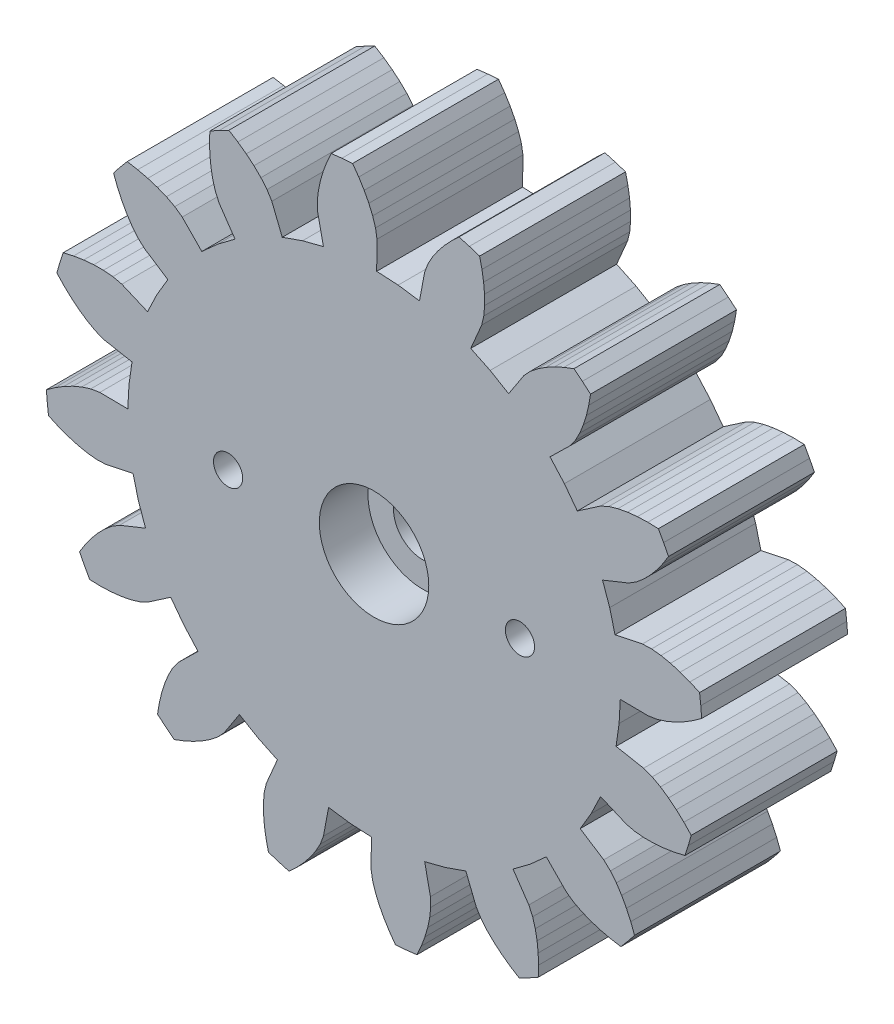
SolidWorks part; units mm, degrees
ref_plane "Front Plane" through (0, 0, 0) normal (0, 0, 1) x (1, 0, 0)
ref_plane "Top Plane" through (0, 0, 0) normal (0, 1, 0) x (1, 0, 0)
ref_plane "Right Plane" through (0, 0, 0) normal (1, 0, 0) x (0, 0, -1)
sketch "Sketch1" plane through (0, 0, 0) normal (0, 0, 1) x (1, 0, 0)
  line L0 (0.1087, 10.1244) -> (0.1211, 11.2757)
  line L1 (0.1211, 11.2757) -> (0.0606, 11.6468)
  line L2 (0.0606, 11.6468) -> (-0.0565, 12.0174)
  line L3 (-0.0565, 12.0174) -> (-0.2135, 12.3863)
  line L4 (-0.2135, 12.3863) -> (-0.4052, 12.7523)
  line L5 (-0.4052, 12.7523) -> (-0.6285, 13.1143)
  line L6 (-0.6285, 13.1143) -> (-0.8817, 13.4712)
  line L7 (-0.8817, 13.4712) -> (-1.3232, 13.435)
  line L8 (-1.3232, 13.435) -> (-1.7633, 13.3843)
  line L9 (-1.7633, 13.3843) -> (-1.942, 12.985)
  line L10 (-1.942, 12.985) -> (-2.0905, 12.5863)
  line L11 (-2.0905, 12.5863) -> (-2.207, 12.19)
  line L12 (-2.207, 12.19) -> (-2.2891, 11.7975)
  line L13 (-2.2891, 11.7975) -> (-2.3316, 11.4112)
  line L14 (-2.3316, 11.4112) -> (-2.3185, 11.0354)
  line L15 (-2.3185, 11.0354) -> (-2.0818, 9.9087)
  line L16 (-2.0818, 9.9087) -> (-2.9391, 9.689)
  line L17 (-2.9391, 9.689) -> (-3.774, 9.3953)
  line L18 (-3.774, 9.3953) -> (-4.2031, 10.4637)
  line L19 (-4.2031, 10.4637) -> (-4.4011, 10.7834)
  line L20 (-4.4011, 10.7834) -> (-4.6511, 11.081)
  line L21 (-4.6511, 11.081) -> (-4.9373, 11.3617)
  line L22 (-4.9373, 11.3617) -> (-5.2544, 11.6266)
  line L23 (-5.2544, 11.6266) -> (-5.5993, 11.8755)
  line L24 (-5.5993, 11.8755) -> (-5.9698, 12.1083)
  line L25 (-5.9698, 12.1083) -> (-6.3639, 11.9059)
  line L26 (-6.3639, 11.9059) -> (-6.7511, 11.6907)
  line L27 (-6.7511, 11.6907) -> (-6.7633, 11.2534)
  line L28 (-6.7633, 11.2534) -> (-6.7479, 10.8283)
  line L29 (-6.7479, 10.8283) -> (-6.7039, 10.4175)
  line L30 (-6.7039, 10.4175) -> (-6.6295, 10.0235)
  line L31 (-6.6295, 10.0235) -> (-6.521, 9.6503)
  line L32 (-6.521, 9.6503) -> (-6.3651, 9.3081)
  line L33 (-6.3651, 9.3081) -> (-5.7152, 8.3577)
  line L34 (-5.7152, 8.3577) -> (-6.4232, 7.8267)
  line L35 (-6.4232, 7.8267) -> (-7.0822, 7.2359)
  line L36 (-7.0822, 7.2359) -> (-7.8875, 8.0587)
  line L37 (-7.8875, 8.0587) -> (-8.1927, 8.2783)
  line L38 (-8.1927, 8.2783) -> (-8.5375, 8.4576)
  line L39 (-8.5375, 8.4576) -> (-8.9094, 8.6074)
  line L40 (-8.9094, 8.6074) -> (-9.3038, 8.7308)
  line L41 (-9.3038, 8.7308) -> (-9.7177, 8.8288)
  line L42 (-9.7177, 8.8288) -> (-10.149, 8.9021)
  line L43 (-10.149, 8.9021) -> (-10.4356, 8.5643)
  line L44 (-10.4356, 8.5643) -> (-10.711, 8.2173)
  line L45 (-10.711, 8.2173) -> (-10.555, 7.8085)
  line L46 (-10.555, 7.8085) -> (-10.3781, 7.4217)
  line L47 (-10.3781, 7.4217) -> (-10.1802, 7.059)
  line L48 (-10.1802, 7.059) -> (-9.9607, 6.7235)
  line L49 (-9.9607, 6.7235) -> (-9.7176, 6.4202)
  line L50 (-9.7176, 6.4202) -> (-9.4426, 6.1637)
  line L51 (-9.4426, 6.1637) -> (-8.4785, 5.5344)
  line L52 (-8.4785, 5.5344) -> (-8.9295, 4.7729)
  line L53 (-8.9295, 4.7729) -> (-9.3121, 3.9749)
  line L54 (-9.3121, 3.9749) -> (-10.371, 4.4269)
  line L55 (-10.371, 4.4269) -> (-10.737, 4.513)
  line L56 (-10.737, 4.513) -> (-11.1243, 4.5467)
  line L57 (-11.1243, 4.5467) -> (-11.5252, 4.5427)
  line L58 (-11.5252, 4.5427) -> (-11.9367, 4.5058)
  line L59 (-11.9367, 4.5058) -> (-12.3566, 4.438)
  line L60 (-12.3566, 4.438) -> (-12.7832, 4.3406)
  line L61 (-12.7832, 4.3406) -> (-12.9187, 3.9188)
  line L62 (-12.9187, 3.9188) -> (-13.0403, 3.4929)
  line L63 (-13.0403, 3.4929) -> (-12.7397, 3.1749)
  line L64 (-12.7397, 3.1749) -> (-12.4283, 2.8853)
  line L65 (-12.4283, 2.8853) -> (-12.1067, 2.6259)
  line L66 (-12.1067, 2.6259) -> (-11.7755, 2.3999)
  line L67 (-11.7755, 2.3999) -> (-11.4348, 2.2128)
  line L68 (-11.4348, 2.2128) -> (-11.0826, 2.081)
  line L69 (-11.0826, 2.081) -> (-9.9511, 1.8685)
  line L70 (-9.9511, 1.8685) -> (-10.0762, 0.9924)
  line L71 (-10.0762, 0.9924) -> (-10.1244, 0.1087)
  line L72 (-10.1244, 0.1087) -> (-11.2757, 0.1211)
  line L73 (-11.2757, 0.1211) -> (-11.6468, 0.0606)
  line L74 (-11.6468, 0.0606) -> (-12.0174, -0.0565)
  line L75 (-12.0174, -0.0565) -> (-12.3863, -0.2135)
  line L76 (-12.3863, -0.2135) -> (-12.7523, -0.4052)
  line L77 (-12.7523, -0.4052) -> (-13.1143, -0.6285)
  line L78 (-13.1143, -0.6285) -> (-13.4712, -0.8817)
  line L79 (-13.4712, -0.8817) -> (-13.435, -1.3232)
  line L80 (-13.435, -1.3232) -> (-13.3843, -1.7633)
  line L81 (-13.3843, -1.7633) -> (-12.985, -1.942)
  line L82 (-12.985, -1.942) -> (-12.5863, -2.0905)
  line L83 (-12.5863, -2.0905) -> (-12.19, -2.207)
  line L84 (-12.19, -2.207) -> (-11.7975, -2.2891)
  line L85 (-11.7975, -2.2891) -> (-11.4112, -2.3316)
  line L86 (-11.4112, -2.3316) -> (-11.0354, -2.3185)
  line L87 (-11.0354, -2.3185) -> (-9.9087, -2.0818)
  line L88 (-9.9087, -2.0818) -> (-9.689, -2.9391)
  line L89 (-9.689, -2.9391) -> (-9.3953, -3.774)
  line L90 (-9.3953, -3.774) -> (-10.4637, -4.2031)
  line L91 (-10.4637, -4.2031) -> (-10.7834, -4.4011)
  line L92 (-10.7834, -4.4011) -> (-11.081, -4.6511)
  line L93 (-11.081, -4.6511) -> (-11.3617, -4.9373)
  line L94 (-11.3617, -4.9373) -> (-11.6266, -5.2544)
  line L95 (-11.6266, -5.2544) -> (-11.8755, -5.5993)
  line L96 (-11.8755, -5.5993) -> (-12.1083, -5.9698)
  line L97 (-12.1083, -5.9698) -> (-11.9059, -6.3639)
  line L98 (-11.9059, -6.3639) -> (-11.6907, -6.7511)
  line L99 (-11.6907, -6.7511) -> (-11.2534, -6.7633)
  line L100 (-11.2534, -6.7633) -> (-10.8283, -6.7479)
  line L101 (-10.8283, -6.7479) -> (-10.4175, -6.7039)
  line L102 (-10.4175, -6.7039) -> (-10.0235, -6.6295)
  line L103 (-10.0235, -6.6295) -> (-9.6503, -6.521)
  line L104 (-9.6503, -6.521) -> (-9.3081, -6.3651)
  line L105 (-9.3081, -6.3651) -> (-8.3577, -5.7152)
  line L106 (-8.3577, -5.7152) -> (-7.8267, -6.4232)
  line L107 (-7.8267, -6.4232) -> (-7.2359, -7.0822)
  line L108 (-7.2359, -7.0822) -> (-8.0587, -7.8875)
  line L109 (-8.0587, -7.8875) -> (-8.2783, -8.1927)
  line L110 (-8.2783, -8.1927) -> (-8.4576, -8.5375)
  line L111 (-8.4576, -8.5375) -> (-8.6074, -8.9094)
  line L112 (-8.6074, -8.9094) -> (-8.7308, -9.3038)
  line L113 (-8.7308, -9.3038) -> (-8.8288, -9.7177)
  line L114 (-8.8288, -9.7177) -> (-8.9021, -10.149)
  line L115 (-8.9021, -10.149) -> (-8.5643, -10.4356)
  line L116 (-8.5643, -10.4356) -> (-8.2173, -10.711)
  line L117 (-8.2173, -10.711) -> (-7.8085, -10.555)
  line L118 (-7.8085, -10.555) -> (-7.4217, -10.3781)
  line L119 (-7.4217, -10.3781) -> (-7.059, -10.1802)
  line L120 (-7.059, -10.1802) -> (-6.7235, -9.9607)
  line L121 (-6.7235, -9.9607) -> (-6.4202, -9.7176)
  line L122 (-6.4202, -9.7176) -> (-6.1637, -9.4426)
  line L123 (-6.1637, -9.4426) -> (-5.5344, -8.4785)
  line L124 (-5.5344, -8.4785) -> (-4.7729, -8.9295)
  line L125 (-4.7729, -8.9295) -> (-3.9749, -9.3121)
  line L126 (-3.9749, -9.3121) -> (-4.4269, -10.371)
  line L127 (-4.4269, -10.371) -> (-4.513, -10.737)
  line L128 (-4.513, -10.737) -> (-4.5467, -11.1243)
  line L129 (-4.5467, -11.1243) -> (-4.5427, -11.5252)
  line L130 (-4.5427, -11.5252) -> (-4.5058, -11.9367)
  line L131 (-4.5058, -11.9367) -> (-4.438, -12.3566)
  line L132 (-4.438, -12.3566) -> (-4.3406, -12.7832)
  line L133 (-4.3406, -12.7832) -> (-3.9188, -12.9187)
  line L134 (-3.9188, -12.9187) -> (-3.4929, -13.0403)
  line L135 (-3.4929, -13.0403) -> (-3.1749, -12.7397)
  line L136 (-3.1749, -12.7397) -> (-2.8853, -12.4283)
  line L137 (-2.8853, -12.4283) -> (-2.6259, -12.1067)
  line L138 (-2.6259, -12.1067) -> (-2.3999, -11.7755)
  line L139 (-2.3999, -11.7755) -> (-2.2128, -11.4348)
  line L140 (-2.2128, -11.4348) -> (-2.081, -11.0826)
  line L141 (-2.081, -11.0826) -> (-1.8685, -9.9511)
  line L142 (-1.8685, -9.9511) -> (-0.9924, -10.0762)
  line L143 (-0.9924, -10.0762) -> (-0.1087, -10.1244)
  line L144 (-0.1087, -10.1244) -> (-0.1211, -11.2757)
  line L145 (-0.1211, -11.2757) -> (-0.0606, -11.6468)
  line L146 (-0.0606, -11.6468) -> (0.0565, -12.0174)
  line L147 (0.0565, -12.0174) -> (0.2135, -12.3863)
  line L148 (0.2135, -12.3863) -> (0.4052, -12.7523)
  line L149 (0.4052, -12.7523) -> (0.6285, -13.1143)
  line L150 (0.6285, -13.1143) -> (0.8817, -13.4712)
  line L151 (0.8817, -13.4712) -> (1.3232, -13.435)
  line L152 (1.3232, -13.435) -> (1.7633, -13.3843)
  line L153 (1.7633, -13.3843) -> (1.942, -12.985)
  line L154 (1.942, -12.985) -> (2.0905, -12.5863)
  line L155 (2.0905, -12.5863) -> (2.207, -12.19)
  line L156 (2.207, -12.19) -> (2.2891, -11.7975)
  line L157 (2.2891, -11.7975) -> (2.3316, -11.4112)
  line L158 (2.3316, -11.4112) -> (2.3185, -11.0354)
  line L159 (2.3185, -11.0354) -> (2.0818, -9.9087)
  line L160 (2.0818, -9.9087) -> (2.9391, -9.689)
  line L161 (2.9391, -9.689) -> (3.774, -9.3953)
  line L162 (3.774, -9.3953) -> (4.2031, -10.4637)
  line L163 (4.2031, -10.4637) -> (4.4011, -10.7834)
  line L164 (4.4011, -10.7834) -> (4.6511, -11.081)
  line L165 (4.6511, -11.081) -> (4.9373, -11.3617)
  line L166 (4.9373, -11.3617) -> (5.2544, -11.6266)
  line L167 (5.2544, -11.6266) -> (5.5993, -11.8755)
  line L168 (5.5993, -11.8755) -> (5.9698, -12.1083)
  line L169 (5.9698, -12.1083) -> (6.3639, -11.9059)
  line L170 (6.3639, -11.9059) -> (6.7511, -11.6907)
  line L171 (6.7511, -11.6907) -> (6.7633, -11.2534)
  line L172 (6.7633, -11.2534) -> (6.7479, -10.8283)
  line L173 (6.7479, -10.8283) -> (6.7039, -10.4175)
  line L174 (6.7039, -10.4175) -> (6.6295, -10.0235)
  line L175 (6.6295, -10.0235) -> (6.521, -9.6503)
  line L176 (6.521, -9.6503) -> (6.3651, -9.3081)
  line L177 (6.3651, -9.3081) -> (5.7152, -8.3577)
  line L178 (5.7152, -8.3577) -> (6.4232, -7.8267)
  line L179 (6.4232, -7.8267) -> (7.0822, -7.2359)
  line L180 (7.0822, -7.2359) -> (7.8875, -8.0587)
  line L181 (7.8875, -8.0587) -> (8.1927, -8.2783)
  line L182 (8.1927, -8.2783) -> (8.5375, -8.4576)
  line L183 (8.5375, -8.4576) -> (8.9094, -8.6074)
  line L184 (8.9094, -8.6074) -> (9.3038, -8.7308)
  line L185 (9.3038, -8.7308) -> (9.7177, -8.8288)
  line L186 (9.7177, -8.8288) -> (10.149, -8.9021)
  line L187 (10.149, -8.9021) -> (10.4356, -8.5643)
  line L188 (10.4356, -8.5643) -> (10.711, -8.2173)
  line L189 (10.711, -8.2173) -> (10.555, -7.8085)
  line L190 (10.555, -7.8085) -> (10.3781, -7.4217)
  line L191 (10.3781, -7.4217) -> (10.1802, -7.059)
  line L192 (10.1802, -7.059) -> (9.9607, -6.7235)
  line L193 (9.9607, -6.7235) -> (9.7176, -6.4202)
  line L194 (9.7176, -6.4202) -> (9.4426, -6.1637)
  line L195 (9.4426, -6.1637) -> (8.4785, -5.5344)
  line L196 (8.4785, -5.5344) -> (8.9295, -4.7729)
  line L197 (8.9295, -4.7729) -> (9.3121, -3.9749)
  line L198 (9.3121, -3.9749) -> (10.371, -4.4269)
  line L199 (10.371, -4.4269) -> (10.737, -4.513)
  line L200 (10.737, -4.513) -> (11.1243, -4.5467)
  line L201 (11.1243, -4.5467) -> (11.5252, -4.5427)
  line L202 (11.5252, -4.5427) -> (11.9367, -4.5058)
  line L203 (11.9367, -4.5058) -> (12.3566, -4.438)
  line L204 (12.3566, -4.438) -> (12.7832, -4.3406)
  line L205 (12.7832, -4.3406) -> (12.9187, -3.9188)
  line L206 (12.9187, -3.9188) -> (13.0403, -3.4929)
  line L207 (13.0403, -3.4929) -> (12.7397, -3.1749)
  line L208 (12.7397, -3.1749) -> (12.4283, -2.8853)
  line L209 (12.4283, -2.8853) -> (12.1067, -2.6259)
  line L210 (12.1067, -2.6259) -> (11.7755, -2.3999)
  line L211 (11.7755, -2.3999) -> (11.4348, -2.2128)
  line L212 (11.4348, -2.2128) -> (11.0826, -2.081)
  line L213 (11.0826, -2.081) -> (9.9511, -1.8685)
  line L214 (9.9511, -1.8685) -> (10.0762, -0.9924)
  line L215 (10.0762, -0.9924) -> (10.1244, -0.1087)
  line L216 (10.1244, -0.1087) -> (11.2757, -0.1211)
  line L217 (11.2757, -0.1211) -> (11.6468, -0.0606)
  line L218 (11.6468, -0.0606) -> (12.0174, 0.0565)
  line L219 (12.0174, 0.0565) -> (12.3863, 0.2135)
  line L220 (12.3863, 0.2135) -> (12.7523, 0.4052)
  line L221 (12.7523, 0.4052) -> (13.1143, 0.6285)
  line L222 (13.1143, 0.6285) -> (13.4712, 0.8817)
  line L223 (13.4712, 0.8817) -> (13.435, 1.3232)
  line L224 (13.435, 1.3232) -> (13.3843, 1.7633)
  line L225 (13.3843, 1.7633) -> (12.985, 1.942)
  line L226 (12.985, 1.942) -> (12.5863, 2.0905)
  line L227 (12.5863, 2.0905) -> (12.19, 2.207)
  line L228 (12.19, 2.207) -> (11.7975, 2.2891)
  line L229 (11.7975, 2.2891) -> (11.4112, 2.3316)
  line L230 (11.4112, 2.3316) -> (11.0354, 2.3185)
  line L231 (11.0354, 2.3185) -> (9.9087, 2.0818)
  line L232 (9.9087, 2.0818) -> (9.689, 2.9391)
  line L233 (9.689, 2.9391) -> (9.3953, 3.774)
  line L234 (9.3953, 3.774) -> (10.4637, 4.2031)
  line L235 (10.4637, 4.2031) -> (10.7834, 4.4011)
  line L236 (10.7834, 4.4011) -> (11.081, 4.6511)
  line L237 (11.081, 4.6511) -> (11.3617, 4.9373)
  line L238 (11.3617, 4.9373) -> (11.6266, 5.2544)
  line L239 (11.6266, 5.2544) -> (11.8755, 5.5993)
  line L240 (11.8755, 5.5993) -> (12.1083, 5.9698)
  line L241 (12.1083, 5.9698) -> (11.9059, 6.3639)
  line L242 (11.9059, 6.3639) -> (11.6907, 6.7511)
  line L243 (11.6907, 6.7511) -> (11.2534, 6.7633)
  line L244 (11.2534, 6.7633) -> (10.8283, 6.7479)
  line L245 (10.8283, 6.7479) -> (10.4175, 6.7039)
  line L246 (10.4175, 6.7039) -> (10.0235, 6.6295)
  line L247 (10.0235, 6.6295) -> (9.6503, 6.521)
  line L248 (9.6503, 6.521) -> (9.3081, 6.3651)
  line L249 (9.3081, 6.3651) -> (8.3577, 5.7152)
  line L250 (8.3577, 5.7152) -> (7.8267, 6.4232)
  line L251 (7.8267, 6.4232) -> (7.2359, 7.0822)
  line L252 (7.2359, 7.0822) -> (8.0587, 7.8875)
  line L253 (8.0587, 7.8875) -> (8.2783, 8.1927)
  line L254 (8.2783, 8.1927) -> (8.4576, 8.5375)
  line L255 (8.4576, 8.5375) -> (8.6074, 8.9094)
  line L256 (8.6074, 8.9094) -> (8.7308, 9.3038)
  line L257 (8.7308, 9.3038) -> (8.8288, 9.7177)
  line L258 (8.8288, 9.7177) -> (8.9021, 10.149)
  line L259 (8.9021, 10.149) -> (8.5643, 10.4356)
  line L260 (8.5643, 10.4356) -> (8.2173, 10.711)
  line L261 (8.2173, 10.711) -> (7.8085, 10.555)
  line L262 (7.8085, 10.555) -> (7.4217, 10.3781)
  line L263 (7.4217, 10.3781) -> (7.059, 10.1802)
  line L264 (7.059, 10.1802) -> (6.7235, 9.9607)
  line L265 (6.7235, 9.9607) -> (6.4202, 9.7176)
  line L266 (6.4202, 9.7176) -> (6.1637, 9.4426)
  line L267 (6.1637, 9.4426) -> (5.5344, 8.4785)
  line L268 (5.5344, 8.4785) -> (4.7729, 8.9295)
  line L269 (4.7729, 8.9295) -> (3.9749, 9.3121)
  line L270 (3.9749, 9.3121) -> (4.4269, 10.371)
  line L271 (4.4269, 10.371) -> (4.513, 10.737)
  line L272 (4.513, 10.737) -> (4.5467, 11.1243)
  line L273 (4.5467, 11.1243) -> (4.5427, 11.5252)
  line L274 (4.5427, 11.5252) -> (4.5058, 11.9367)
  line L275 (4.5058, 11.9367) -> (4.438, 12.3566)
  line L276 (4.438, 12.3566) -> (4.3406, 12.7832)
  line L277 (4.3406, 12.7832) -> (3.9188, 12.9187)
  line L278 (3.9188, 12.9187) -> (3.4929, 13.0403)
  line L279 (3.4929, 13.0403) -> (3.1749, 12.7397)
  line L280 (3.1749, 12.7397) -> (2.8853, 12.4283)
  line L281 (2.8853, 12.4283) -> (2.6259, 12.1067)
  line L282 (2.6259, 12.1067) -> (2.3999, 11.7755)
  line L283 (2.3999, 11.7755) -> (2.2128, 11.4348)
  line L284 (2.2128, 11.4348) -> (2.081, 11.0826)
  line L285 (2.081, 11.0826) -> (1.8685, 9.9511)
  line L286 (1.8685, 9.9511) -> (0.9924, 10.0762)
  line L287 (0.9924, 10.0762) -> (0.1087, 10.1244)
extrude "Boss-Extrude1" add sketch "Sketch1" along normal blind 6 from offset 14
sketch "Sketch2" plane through (0, 0, 0) normal (0, 0, 1) x (1, 0, 0)
  circle A0 centre (0, 0) radius 1.2
extrude "Cut-Extrude1" cut sketch "Sketch2" against normal through all and the other way through all
sketch "Sketch3" plane through (0, 0, 0) normal (0, 0, 1) x (1, 0, 0)
  circle A0 centre (0, 0) radius 2.25
extrude "Cut-Extrude2" cut sketch "Sketch3" along normal blind 2 from offset 18
sketch "Sketch4" plane through (0, 0, 0) normal (0, 0, 1) x (1, 0, 0)
  circle A0 centre (0, 0) radius 3.8
extrude "Cut-Extrude3" cut sketch "Sketch4" along normal blind 2.5 from offset 14
sketch "Sketch5" plane through (0, 0, 0) normal (0, 0, 1) x (1, 0, 0)
  circle A0 centre (6, 0) radius 0.6
  circle A1 centre (-6, 0) radius 0.6
extrude "Cut-Extrude4" cut sketch "Sketch5" against normal through all and the other way through all
